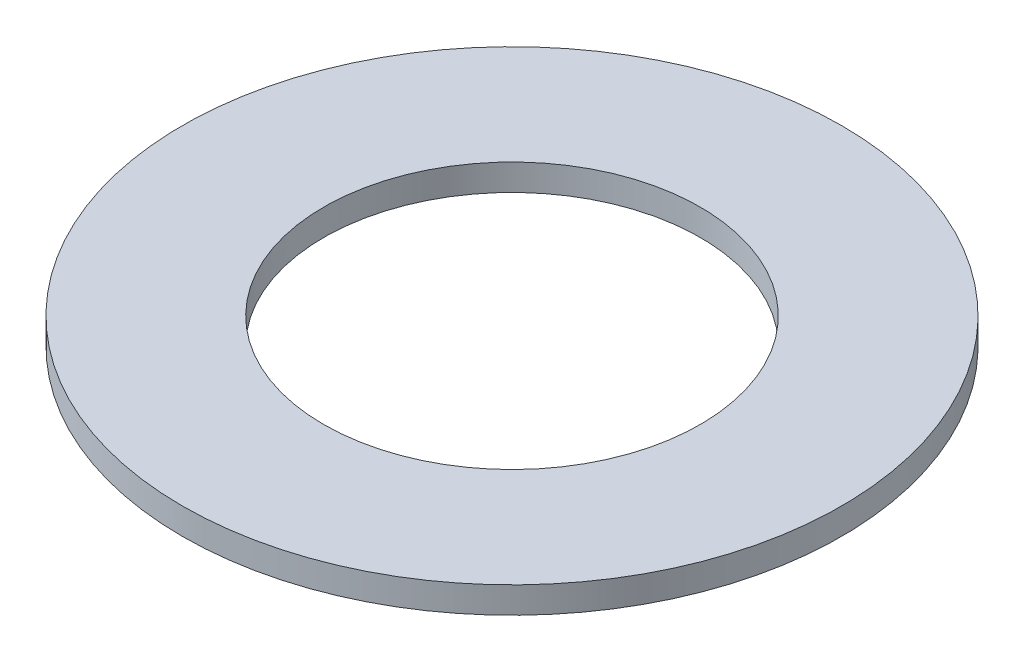
SolidWorks part; units mm, degrees
ref_plane "Front Plane" through (0, 0, 0) normal (0, 0, 1) x (1, 0, 0)
ref_plane "Top Plane" through (0, 0, 0) normal (0, 1, 0) x (1, 0, 0)
ref_plane "Right Plane" through (0, 0, 0) normal (1, 0, 0) x (0, 0, -1)
sketch "Sketch1" plane through (0, 0, 0) normal (0, 1, 0) x (1, 0, 0)
  circle A0 centre (0, 0) radius 87.5
  dimension "FLANGE_OD" = 175
extrude "Boss-Extrude1" add sketch "Sketch1" along normal blind 7
sketch "Sketch2" plane through (0, 0, 0) normal (0, 1, 0) x (1, 0, 0)
  circle A0 centre (0, 0) radius 50
  dimension "BORE_D" = 100
extrude "Cut-Extrude1" cut sketch "Sketch2" along normal through all
sketch "Sketch3" plane through (0, 7, 0) normal (0, 1, 0) x (1, 0, 0)
  circle A0 centre (0, 0) radius 29.4564 construction
  circle A1 centre (-29.4564, 0) radius 1.8928
  dimension "BOLT_D" = 3.7856
  dimension "BOLT_PCD" = 58.9127
extrude "Cut-Extrude2" cut sketch "Sketch3" against normal blind 5.9041 rebuild error yes
pattern_circular "CirPattern1" count 5 over 360 rebuild error yes
